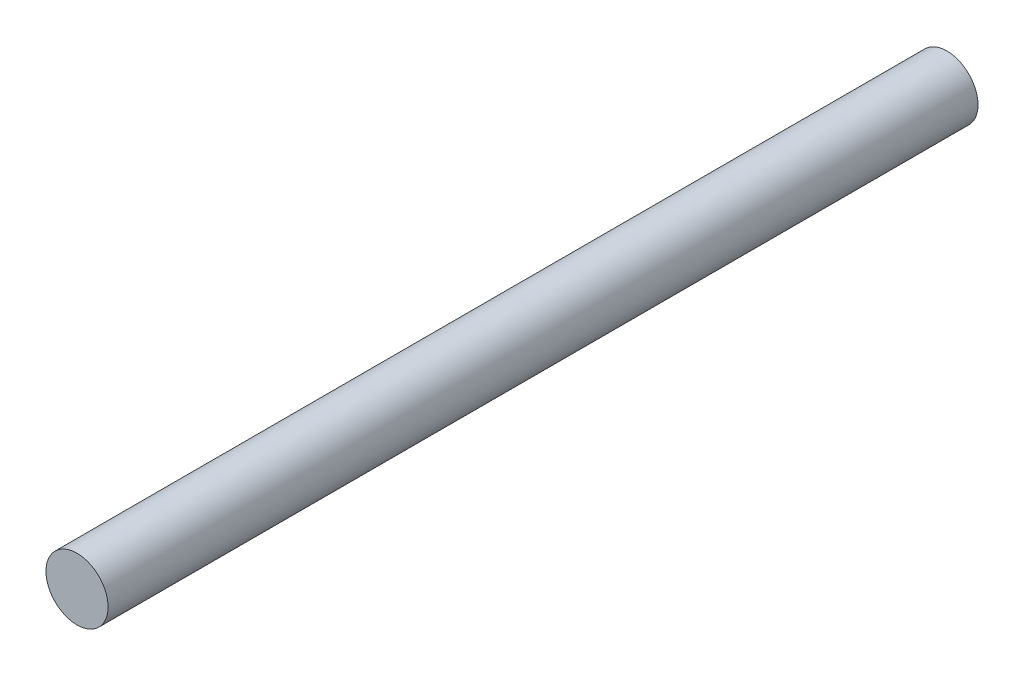
SolidWorks part; units mm, degrees
ref_plane "Alzado" through (0, 0, 0) normal (0, 0, 1) x (1, 0, 0)
ref_plane "Planta" through (0, 0, 0) normal (0, 1, 0) x (1, 0, 0)
ref_plane "Vista lateral" through (0, 0, 0) normal (1, 0, 0) x (0, 0, -1)
sketch "Croquis1" plane through (0, 0, 0) normal (0, 0, 1) x (1, 0, 0)
  circle A0 centre (0, 0) radius 4
  dimension "D1" = 8
extrude "Saliente-Extruir1" add sketch "Croquis1" along normal mid plane 112
ref_plane "Plano2" through (3, 0, 0) normal (1, 0, 0) x (0, 0, -1)
